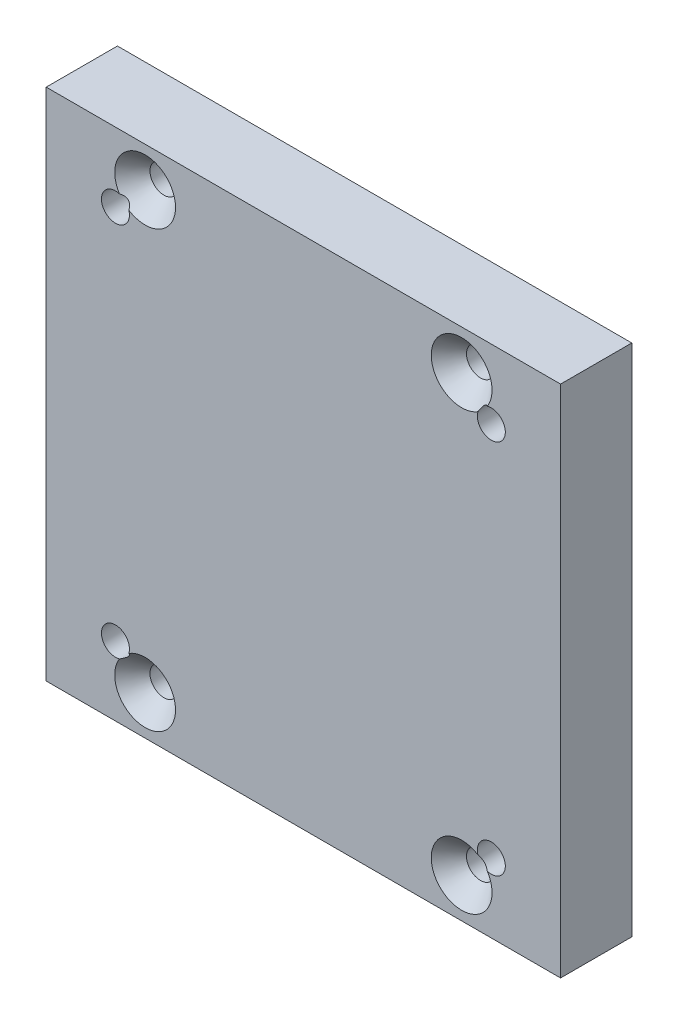
SolidWorks part; units mm, degrees
material "6061-T6 (SS)"
ref_plane "Front Plane" through (0, 0, 0) normal (0, 0, 1) x (1, 0, 0)
ref_plane "Top Plane" through (0, 0, 0) normal (0, 1, 0) x (1, 0, 0)
ref_plane "Right Plane" through (0, 0, 0) normal (1, 0, 0) x (0, 0, -1)
sketch "Sketch1" plane through (0, 0, 0) normal (0, 0, 1) x (1, 0, 0)
  line L0 (-38.1, 0) -> (0, 0) construction
  line L1 (0, 0) -> (-30.48, 30.48) construction
  line L3 (41.275, -41.275) -> (-41.275, -41.275)
  line L4 (41.275, -41.275) -> (41.275, 41.275)
  line L5 (41.275, 41.275) -> (-41.275, 41.275)
  line L6 (-41.275, -41.275) -> (-41.275, 41.275)
  line L7 (41.275, -41.275) -> (-41.275, 41.275) construction
  line L8 (41.275, 41.275) -> (-41.275, -41.275) construction
  circle A0 centre (0, 0) radius 38.1 construction
  circle A1 centre (-30.48, 30.48) radius 2.5527 construction
  dimension "D1" = 76.2
  dimension "D2" = 5.1054
  dimension "D4" = 82.55
  dimension "D3" = 45
  dimension "D5" = 30.48
extrude "Boss-Extrude1" add sketch "Sketch1" along normal blind 11.43
sketch "Sketch2" plane through (0, 0, 0) normal (0, 0, -1) x (-1, 0, 0)
  circle A0 centre (0, 0) radius 38.1
  dimension "D1" = 76.2
extrude "Cut-Extrude1" cut sketch "Sketch2" against normal blind 8.89
hole_wizard "CSK for #8 Flat Head Machine Screw1" positions "Sketch4" profile "Sketch3" countersink size "#8" standard "ANSI Inch" end condition through all
sketch "Sketch4" plane through (0, 0, 11.43) normal (0, 0, 1) x (1, 0, 0)
  line L0 (-25.4, 34.925) -> (25.4, -34.925) construction
  line L3 (25.4, 34.925) -> (-25.4, -34.925) construction
  point P0 (25.4, 34.925)
  point P1 (-25.4, 34.925)
  point P3 (-25.4, -34.925)
  point P5 (25.4, -34.925)
  dimension "D1" = 50.8
  dimension "D2" = 69.85
sketch "Sketch3" plane through (25.4, 34.925, 11.43) normal (1, 0, 0) x (0, -1, 0)
  line L0 (0, 0) -> (0, 11.43)
  line L1 (0, 11.43) -> (2.2479, 11.43)
  line L2 (2.2479, 11.43) -> (2.2479, 3.0265)
  line L3 (2.2479, 3.0265) -> (4.8788, 0)
  line L5 (4.8788, 0) -> (0, 0)
  line L6 (-2.2479, 3.0265) -> (-4.8788, 0) construction
  line L11 (0, -6.35) -> (0, 107.95) construction
  dimension "Thru Hole Dia." = 4.4958
  dimension "Thru Hole Depth" = 11.43
  dimension "Near C'Sink Dia." = 9.7576
  dimension "Near C'Sink Angle" = 82
hole_wizard "#8 Clearance Hole1" positions "Sketch7" profile "Sketch6" hole size "#8" standard "ANSI Inch" end condition through all
sketch "Sketch7" plane through (0, 0, 11.43) normal (0, 0, 1) x (1, 0, 0)
  line L1 (-30.1625, 30.1625) -> (30.1625, 30.1625)
  line L2 (-30.1625, 30.1625) -> (-30.1625, -30.1625)
  line L3 (-30.1625, -30.1625) -> (30.1625, -30.1625)
  line L4 (30.1625, 30.1625) -> (30.1625, -30.1625)
  line L5 (-30.1625, 30.1625) -> (30.1625, -30.1625) construction
  line L6 (-30.1625, -30.1625) -> (30.1625, 30.1625) construction
  point P2 (30.1625, -30.1625)
  point P49 (-30.1625, 30.1625)
  point P50 (-30.1625, -30.1625)
  point P51 (30.1625, 30.1625)
  dimension "D1" = 60.325
  dimension "D2" = 60.325
sketch "Sketch6" plane through (30.1625, -30.1625, 11.43) normal (1, 0, 0) x (0, -1, 0)
  line L0 (0, 0) -> (0, 11.43)
  line L1 (0, 11.43) -> (2.2479, 11.43)
  line L2 (2.2479, 11.43) -> (2.2479, 0)
  line L5 (2.2479, 0) -> (0, 0)
  line L11 (0, -6.35) -> (0, 107.95) construction
  dimension "Thru Hole Dia." = 4.4958
  dimension "Thru Hole Depth" = 11.43
